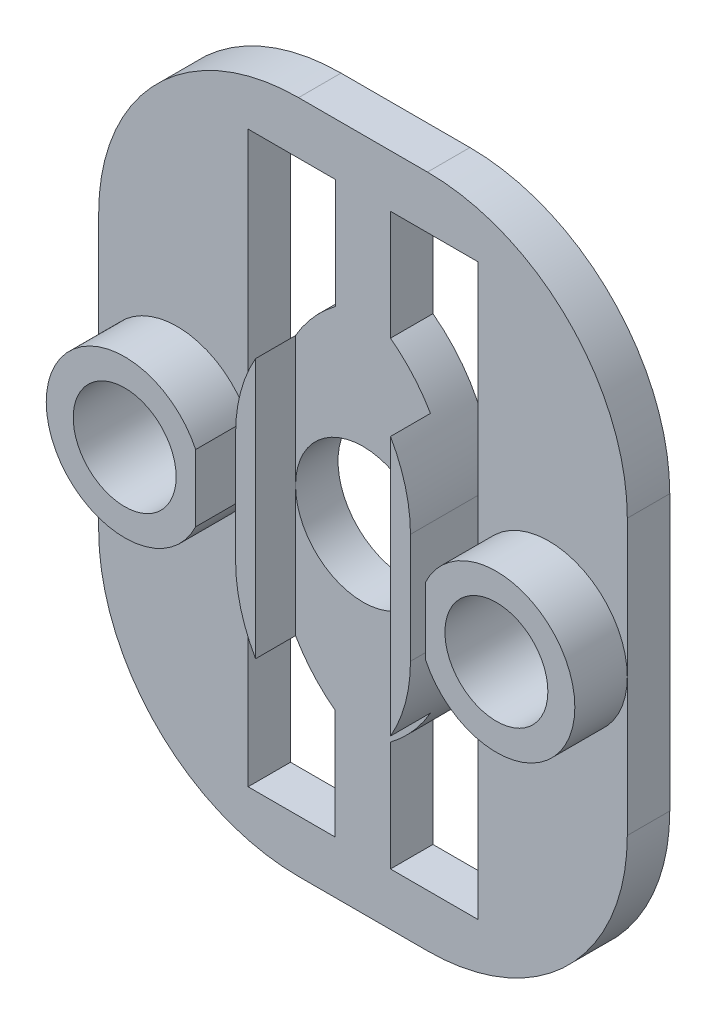
SolidWorks part; units mm, degrees
ref_plane "Front Plane" through (0, 0, 0) normal (0, 0, 1) x (1, 0, 0)
ref_plane "Top Plane" through (0, 0, 0) normal (0, 1, 0) x (1, 0, 0)
ref_plane "Right Plane" through (0, 0, 0) normal (1, 0, 0) x (0, 0, -1)
sketch "Sketch1" plane through (0, 0, 0) normal (0, 0, 1) x (1, 0, 0)
  line L0 (13.8938, 8.89) -> (-5.0038, 8.89) construction
  line L7 (0, 0) -> (0, 17.78)
  line L9 (8.89, 0) -> (8.89, 17.78)
  line L10 (0, 0) -> (8.89, 17.78) construction
  line L11 (0, 17.78) -> (8.89, 0) construction
  line L12 (-1.016, -8.255) -> (-8.9916, -8.255)
  line L13 (-1.016, 0.508) -> (-1.016, 18.288)
  line L14 (-1.016, 26.035) -> (-8.9916, 26.035)
  line L15 (-8.9916, -8.255) -> (-8.9916, 26.035)
  line L16 (-1.016, -8.255) -> (-8.9916, 26.035) construction
  line L17 (-1.016, 26.035) -> (-8.9916, -8.255) construction
  line L18 (9.906, -8.255) -> (17.8816, -8.255)
  line L19 (9.906, 0) -> (9.906, 17.78)
  line L20 (9.906, 26.035) -> (17.8816, 26.035)
  line L21 (17.8816, -8.255) -> (17.8816, 26.035)
  line L22 (9.906, -8.255) -> (17.8816, 26.035) construction
  line L23 (9.906, 26.035) -> (17.8816, -8.255) construction
  line L24 (-1.016, 26.035) -> (9.906, 26.035)
  line L28 (-1.016, -8.255) -> (9.906, -8.255)
  line L34 (0, 0) -> (3.0161, 0)
  line L35 (-1.016, 0.508) -> (-1.016, -5.588)
  line L36 (-1.016, -5.588) -> (3.0161, -5.588)
  line L37 (3.0161, 0) -> (3.0161, -5.588)
  line L38 (8.89, 0) -> (5.842, 0)
  line L39 (9.906, 0) -> (9.906, -5.588)
  line L40 (9.906, -5.588) -> (5.842, -5.588)
  line L41 (5.842, 0) -> (5.842, -5.588)
  line L42 (0, 17.78) -> (3.048, 17.78)
  line L43 (-1.016, 18.288) -> (-1.016, 23.368)
  line L44 (-1.016, 23.368) -> (3.048, 23.368)
  line L45 (3.048, 17.78) -> (3.048, 23.368)
  line L46 (8.89, 17.78) -> (5.842, 17.78)
  line L47 (9.906, 17.78) -> (9.906, 23.368)
  line L48 (9.906, 23.368) -> (5.842, 23.368)
  line L49 (5.842, 17.78) -> (5.842, 23.368)
  circle A0 centre (13.8938, 8.89) radius 2.6162
  circle A1 centre (-5.0038, 8.89) radius 2.6162
  point P0 (4.445, 8.89)
  dimension "D1" = 5.2324
  dimension "D2" = 5.2324
  dimension "D3" = 18.8976
  dimension "D4" = 8.89
  dimension "D5" = 17.78
  dimension "D6" = 1.016
  dimension "D7" = 1.016
  dimension "D8" = 34.29
  dimension "D9" = 10.9338
  dimension "D10" = 10.9338
  dimension "D11" = 7.9756
  dimension "D12" = 1.3716
  dimension "D13" = 1.3716
  dimension "D14" = 5.588
  dimension "D15" = 5.588
  dimension "D16" = 4.064
  dimension "D17" = 4.064
  dimension "D18" = 4.064
  dimension "D19" = 4.064
  dimension "D20" = 5.588
  dimension "D21" = 5.588
  dimension "D22" = 1.016
extrude "Boss-Extrude1" add sketch "Sketch1" along normal blind 2.159
sketch "Sketch2" plane through (0, 0, 2.159) normal (0, 0, 1) x (1, 0, 0)
  line L0 (-8.9916, 8.89) -> (17.8816, 8.89) construction
  line L1 (-8.9916, 26.035) -> (-8.9916, -8.255) construction
  line L2 (17.8816, -8.255) -> (17.8816, 26.035) construction
  circle A0 centre (4.445, 8.89) radius 3.429
  point P8 (0, 0)
  point P9 (0, 0)
  dimension "D1" = 6.858
extrude "Cut-Extrude1" cut sketch "Sketch2" against normal through all
fillet "Fillet1" radius 10.16 4 edges at (17.8816, 26.035, 1.0795) (-8.9916, 26.035, 1.0795) (17.8816, -8.255, 1.0795) (-8.9916, -8.255, 1.0795)
sketch "Sketch3" plane through (0, 0, 2.159) normal (0, 0, 1) x (1, 0, 0)
  line L1 (0, 17.78) -> (1.016, 17.78)
  line L2 (0, 17.78) -> (0, 0)
  line L3 (0, 0) -> (1.016, 0)
  line L4 (1.016, 17.78) -> (1.016, 0)
  line L5 (8.89, 17.78) -> (7.874, 17.78)
  line L6 (8.89, 17.78) -> (8.89, 0)
  line L7 (8.89, 0) -> (7.874, 0)
  line L8 (7.874, 17.78) -> (7.874, 0)
  circle A0 centre (4.445, 8.89) radius 3.429 construction
extrude "Boss-Extrude2" add sketch "Sketch3" along normal blind 2.032
sketch "Sketch4" plane through (0, 0, 2.159) normal (0, 0, 1) x (1, 0, 0)
  line L0 (9.906, -5.588) -> (9.906, 23.368) construction
  line L1 (-8.9916, 15.875) -> (-8.9916, 1.905) construction
  circle A0 centre (-5.0038, 8.89) radius 3.9878
  circle A1 centre (13.8938, 8.89) radius 3.9878
  circle A2 centre (-5.0038, 8.89) radius 2.6162
  circle A3 centre (13.8938, 8.89) radius 2.6162
  circle A4 centre (13.8938, 8.89) radius 2.6162 construction
  circle A5 centre (-5.0038, 8.89) radius 2.6162 construction
extrude "Boss-Extrude3" add sketch "Sketch4" along normal blind 2.667
fillet "Fillet2" radius 7.62 4 edges at (8.89, 0, 2.0955) (0, 0, 2.0955) (0, 17.78, 2.0955) (8.89, 17.78, 2.0955)
sketch "Sketch6" plane through (0, 0, 0) normal (0, 0, -1) x (-1, 0, 0)
  line L0 (-5.842, -5.588) -> (-9.906, -5.588) construction
  line L1 (1.016, -5.588) -> (1.397, -5.588)
  line L2 (1.016, -5.588) -> (1.016, 23.368)
  line L3 (1.016, 23.368) -> (1.397, 23.368)
  line L4 (1.397, -5.588) -> (1.397, 23.368)
  line L5 (-9.906, 23.368) -> (-10.287, 23.368)
  line L6 (-9.906, 23.368) -> (-9.906, -5.588)
  line L7 (-9.906, -5.588) -> (-10.287, -5.588)
  line L8 (-10.287, 23.368) -> (-10.287, -5.588)
  line L9 (-3.048, 23.368) -> (1.016, 23.368) construction
  dimension "D1" = 0.381
  dimension "D2" = 0.381
extrude "Cut-Extrude2" cut sketch "Sketch6" against normal through all
